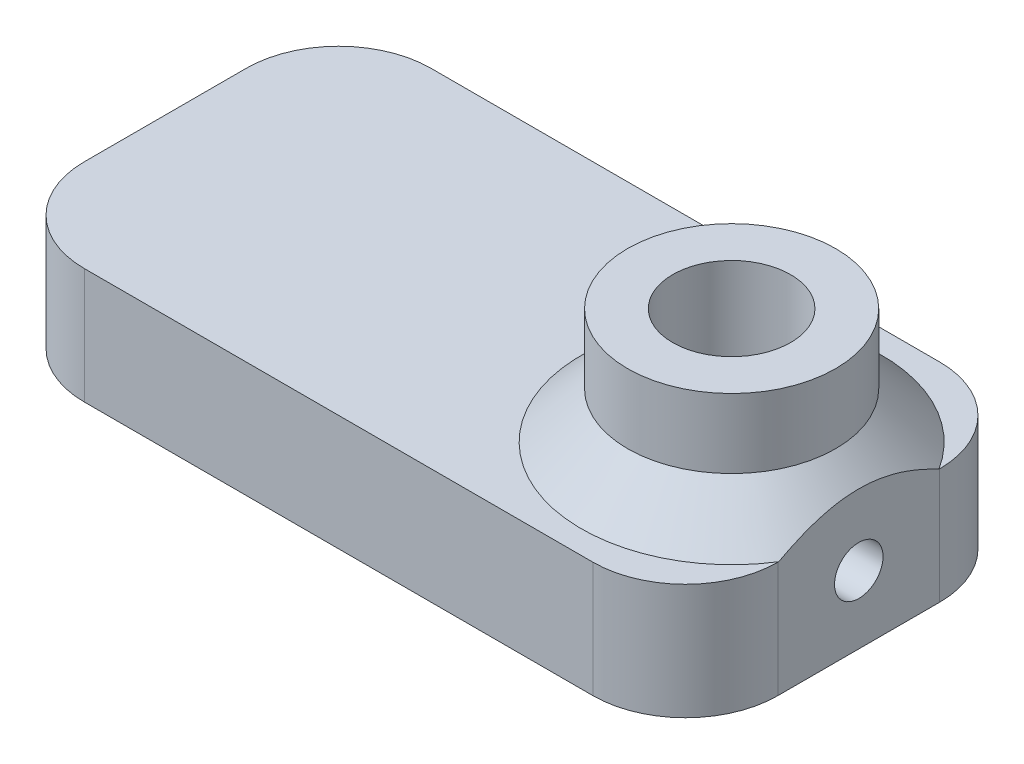
SolidWorks part; units mm, degrees
ref_plane "Front Plane" through (0, 0, 0) normal (0, 0, 1) x (1, 0, 0)
ref_plane "Top Plane" through (0, 0, 0) normal (0, 1, 0) x (1, 0, 0)
ref_plane "Right Plane" through (0, 0, 0) normal (1, 0, 0) x (0, 0, -1)
sketch "Sketch1" plane through (0, 0, 0) normal (0, 1, 0) x (1, 0, 0)
  line L1 (-49, 15) -> (11, 15)
  line L2 (-49, 15) -> (-49, -15)
  line L3 (-49, -15) -> (11, -15)
  line L4 (11, 15) -> (11, -15)
  circle A1 centre (0, 0) radius 9
  point P8 (11, 0)
  dimension "D2" = 18
  dimension "D3" = 30
  dimension "D4" = 60
  dimension "D1" = 11
extrude "Base" add sketch "Sketch1" along normal blind 10 contours L4 A1 L1 L2 L3 | A1 region at (-22.1283, 0, 0) region at (0, 0, 0)
fillet "AddALittleBeauty" radius 8 4 edges at (-49, 5, 15) (-49, 5, -15) (11, 5, -15) (11, 5, 15)
extrude "RodHolder" add sketch "Sketch1<3>" along normal blind 20 contours A1 region at (0, 0, 0)
sketch "Sketch1<3>" plane through (0, 0, 0) normal (0, 1, 0) x (1, 0, 0) same geometry as "Sketch1"
hole_wizard "M5x0.8 Tapped Hole for fixing rod" positions "Sketch3" profile "Sketch4" tap size "M5x0.8" standard "ANSI Metric"
sketch "Sketch3" plane through (11, 0, 0) normal (1, 0, 0) x (0, 0, -1)
  point P0 (0, 5.8799)
cosmetic thread "Hole Thread1" parameters "D1"=6.3524, "D2"=5
sketch "Sketch4" plane through (11, 5.8799, 0) normal (0, 1, 0) x (0, 0, -1)
  line L0 (0, 0) -> (0, 11.6618)
  line L1 (0, 11.6618) -> (2.1, 10.4)
  line L2 (2.1, 10.4) -> (2.1, 0)
  line L5 (2.1, 0) -> (0, 0)
  line L10 (0, 11.6618) -> (-2.1, 10.4) construction
  line L11 (0, -6.35) -> (0, 107.95) construction
  dimension "Tap Drill Dia." = 4.2
  dimension "Tap Drill Depth" = 10.4
  dimension "Drill Angle" = 118
chamfer "Chamfer1" distance 4 angle 45 1 edges at (0, 10, 9)
hole_wizard "Ø10.2 (10.2) Rod Hole" positions "Sketch5" profile "Sketch6" hole size "Ø10.2" standard "ANSI Metric" end condition through all
sketch "Sketch5" plane through (0, 20, 0) normal (0, 1, 0) x (1, 0, 0)
  point P0 (0, 0)
sketch "Sketch6" plane through (0, 20, 0) normal (1, 0, 0) x (0, 0, 1)
  line L0 (0, 0) -> (0, 20)
  line L1 (0, 20) -> (5.1, 20)
  line L2 (5.1, 20) -> (5.1, 0)
  line L5 (5.1, 0) -> (0, 0)
  line L11 (0, -6.35) -> (0, 107.95) construction
  dimension "Thru Hole Dia." = 10.2
  dimension "Thru Hole Depth" = 20
equation "\"D2@Sketch1\"=10.00mm+8"
